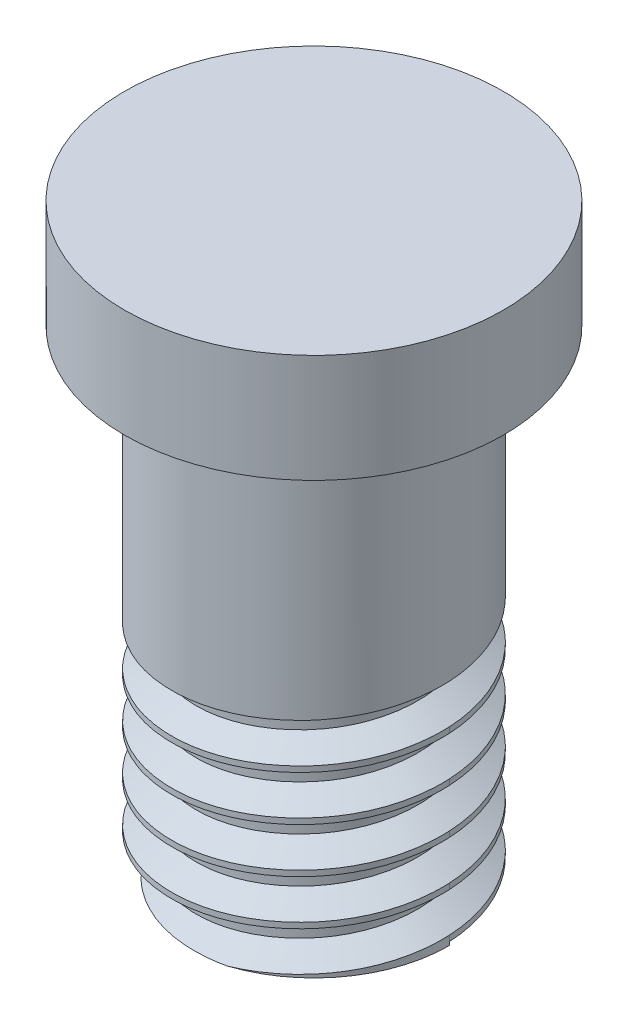
SolidWorks part; units mm, degrees
ref_plane "Front Plane" through (0, 0, 0) normal (0, 0, 1) x (1, 0, 0)
ref_plane "Top Plane" through (0, 0, 0) normal (0, 1, 0) x (1, 0, 0)
ref_plane "Right Plane" through (0, 0, 0) normal (1, 0, 0) x (0, 0, -1)
sketch "Sketch1" plane through (0, 0, 0) normal (0, 1, 0) x (1, 0, 0)
  circle A0 centre (0, 0) radius 3.75
  dimension "D1" = 7.5
extrude "Boss-Extrude1" add sketch "Sketch1" along normal blind 13
sketch "Sketch2" plane through (0, 13, 0) normal (0, 1, 0) x (1, 0, 0)
  circle A0 centre (0, 0) radius 5.25
  circle A1 centre (0, 0) radius 3.75 construction
  dimension "D1" = 1.5
extrude "Boss-Extrude2" add sketch "Sketch2" along normal blind 3
thread "Thread1" pitch 1.25 method cut profile "Thread Profile1" start angle 0, offset 1, length 7, pitch 1.25, diameter 7.5
ref_plane "Plane1" through (3.75, -1, 0) normal (0, 0, 1) x (1, 0, 0)
sketch "Thread Profile1" plane through (3.75, -1, 0) normal (0, 0, 1) x (1, 0, 0)
  line L0 (0, 0) -> (0, 1.25) construction
  line L11 (0, 0) -> (0, 1.0937)
  line L12 (0, 1.0937) -> (-0.6766, 0.7031)
  line L13 (-0.6766, 0.7031) -> (-0.6766, 0.3906)
  line L15 (-0.6766, 0.3906) -> (0, 0)
  line L17 (-0.6766, 0.5469) -> (0, 0.5469) construction
  point P2 (0, 0)
  dimension "Pitch" = 1.25
  dimension "Profile_Angle" = 60
  dimension "Profile_Land" = 0.3125
  dimension "Profile_Height" = 0.6766
